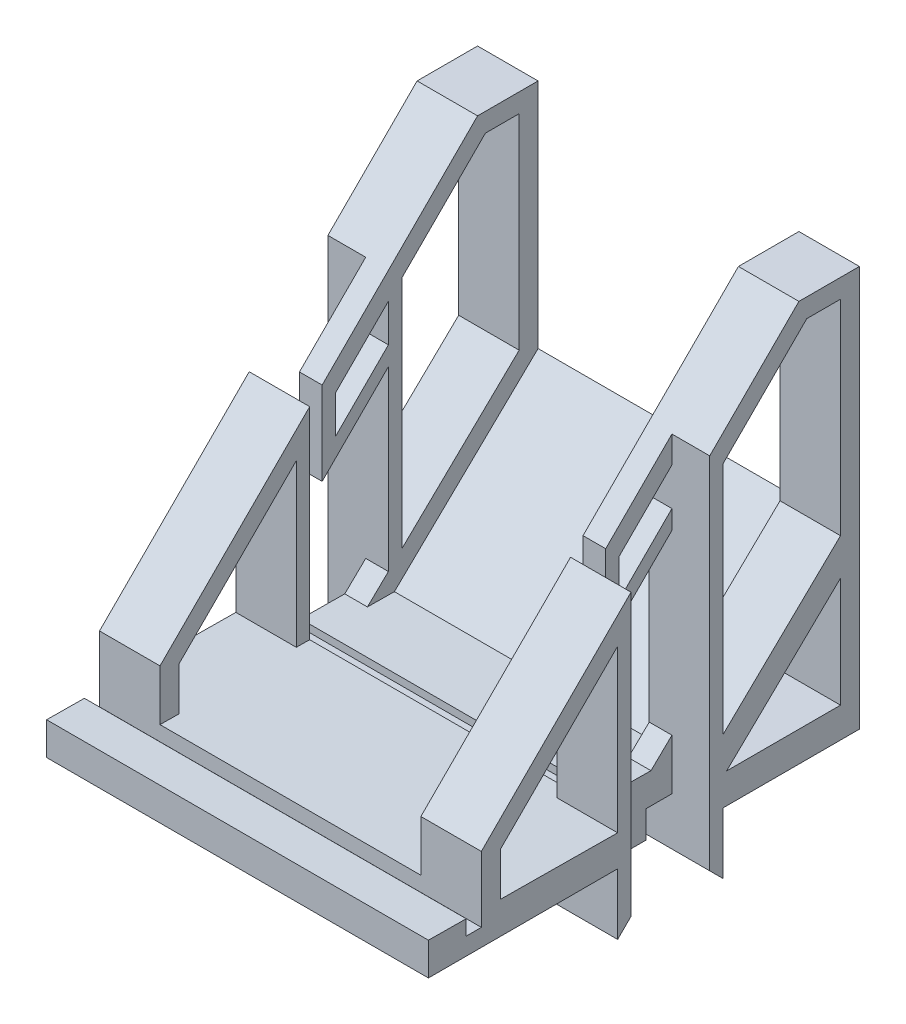
SolidWorks part; units mm, degrees
note: The reader was unsure of these and kept them because the rebuilt part matched: shared geometry of "Sketch1<3>", "Sketch9<3>".
ref_plane "Front Plane" through (0, 0, 0) normal (0, 0, 1) x (1, 0, 0)
ref_plane "Top Plane" through (0, 0, 0) normal (0, 1, 0) x (1, 0, 0)
ref_plane "Right Plane" through (0, 0, 0) normal (1, 0, 0) x (0, 0, -1)
sketch "Sketch1" plane through (0, 0, 0) normal (1, 0, 0) x (0, 0, -1)
  line L0 (0, 0) -> (5, 0)
  line L1 (5, 0) -> (5, -1.7)
  line L2 (5, -1.7) -> (7, -1.7)
  line L3 (7, -1.7) -> (7, 0)
  line L4 (7, 0) -> (38, 0)
  line L5 (38, 0) -> (57, 18.3481)
  line L6 (57, 18.3481) -> (57, -4)
  line L7 (57, -4) -> (33.8, -4)
  line L9 (33.8, -7.6) -> (30.2, -7.6)
  line L11 (30.2, -4) -> (0, -4)
  line L12 (0, -4) -> (0, 0)
  line L13 (30.2, -4) -> (33.8, -4) construction
  line L14 (54.5, 14.5437) -> (39.4396, 0)
  line L15 (39.4396, 0) -> (54.5, 0)
  line L16 (54.5, 0) -> (54.5, 14.5437)
  line L17 (26.795, -4) -> (26.795, -10.3322)
  line L18 (26.795, -10.3322) -> (25.0272, -12.1)
  line L19 (25.0272, -12.1) -> (25.0272, -4)
  line L20 (25.0272, -4) -> (26.795, -4)
  line L21 (37.205, -4) -> (37.205, -10.3322)
  line L22 (37.205, -10.3322) -> (38.9728, -12.1)
  line L23 (38.9728, -12.1) -> (38.9728, -4)
  line L24 (38.9728, -4) -> (37.205, -4)
  line L25 (26.795, -10.3322) -> (37.205, -10.3322) construction
  line L26 (33.8, -4) -> (33.8, -7.6)
  line L27 (30.2, -4) -> (30.2, -7.6)
  line L28 (38, 0) -> (7, 0.2705)
  line L29 (7, 0.2705) -> (7, 0)
  line L31 (38, 0) -> (7, 0)
  line L32 (5, 0) -> (5, 0.288)
  line L33 (5, 0.288) -> (0, 0.3316)
  line L34 (0, 0.3316) -> (0, 0)
  point P15 (32, -7.6)
  point P22 (32, -10.3322)
  point P30 (32, -4)
  dimension "D1" = 1.7
  dimension "D2" = 5
  dimension "D3" = 2
  dimension "D4" = 57
  dimension "D5" = 136
  dimension "D6" = 38
  dimension "D7" = 4
  dimension "D8" = 3.6
  dimension "D9" = 135
  dimension "D10" = 3.6
  dimension "D11" = 135
  dimension "D12" = 25
  dimension "D13" = 8.1
  dimension "D14" = 1
  dimension "D15" = 2.5
  dimension "D16" = 0.5
  dimension "D17" = 2.5
  dimension "D18" = 10.41
extrude "Boss-Extrude1" add sketch "Sketch1" along normal blind 17.25
sketch "Sketch3" plane through (17.25, 0, 0) normal (1, 0, 0) x (0, 0, -1)
  line L0 (57, -4) -> (57, 49)
  line L1 (57, 18.3481) -> (57, -4) construction
  line L2 (49, 49) -> (7, 7)
  line L3 (7, 7) -> (7, -1.7)
  line L5 (0, -4) -> (25.0272, -4)
  line L6 (38.9728, -4) -> (57, -4)
  line L8 (25.0272, -12.1) -> (25.0272, -4) construction
  line L9 (37.205, -10.3322) -> (38.9728, -12.1) construction
  line L10 (26.795, -10.3322) -> (25.0272, -12.1) construction
  line L11 (26.795, -4) -> (26.795, -10.3322) construction
  line L12 (30.2, -4) -> (26.795, -4) construction
  line L13 (33.8, -4) -> (33.8, -7.6)
  line L14 (33.8, -7.6) -> (30.2, -7.6) construction
  line L16 (37.205, -4) -> (33.8, -4) construction
  line L17 (38.9728, -12.1) -> (38.9728, -4) construction
  line L18 (37.205, -4) -> (37.205, -10.3322) construction
  line L19 (25.0272, -12.1) -> (25.0272, -4)
  line L20 (37.205, -10.3322) -> (38.9728, -12.1)
  line L21 (26.795, -10.3322) -> (25.0272, -12.1)
  line L22 (26.795, -4) -> (26.795, -10.3322)
  line L23 (30.2, -4) -> (26.795, -4)
  line L25 (33.8, -7.6) -> (30.2, -7.6)
  line L27 (37.205, -4) -> (33.8, -4)
  line L28 (38.9728, -12.1) -> (38.9728, -4)
  line L29 (37.205, -4) -> (37.205, -10.3322)
  line L30 (9.5, 5.9645) -> (9.5, 0)
  line L31 (7, 0) -> (38, 0) construction
  line L32 (9.5, 0) -> (34.4011, 0)
  line L33 (34.4011, 0) -> (54.5, 19.4093)
  line L34 (54.5, 19.4093) -> (54.5, 46.5)
  line L35 (50.0355, 46.5) -> (9.5, 5.9645)
  line L36 (0, -4) -> (0, 0) construction
  line L37 (38, 0) -> (57, 18.3481) construction
  line L38 (0, 0) -> (5, 0) construction
  line L39 (7, -1.7) -> (7, 0) construction
  line L40 (49, 49) -> (57, 49)
  line L41 (54.5, 46.5) -> (50.0355, 46.5)
  line L42 (5, 0) -> (5, -1.7) construction
  line L43 (5, -1.7) -> (7, -1.7) construction
  line L44 (0, -4) -> (0, 0)
  line L45 (0, 0) -> (5, 0)
  line L46 (5, 0) -> (5, -1.7)
  line L47 (5, -1.7) -> (7, -1.7)
  line L53 (30.2, -4) -> (30.2, -7.6)
  line L54 (39.4396, 0) -> (54.5, 0) construction
  line L55 (54.5, 0) -> (54.5, 14.5437) construction
  line L56 (54.5, 14.5437) -> (39.4396, 0) construction
  line L57 (39.4396, 0) -> (54.5, 0)
  line L58 (54.5, 0) -> (54.5, 14.5437)
  line L59 (54.5, 14.5437) -> (39.4396, 0)
  point P6 (53, 49)
  dimension "D1" = 45
  dimension "D7" = 8
  dimension "D2" = 11
  dimension "D3" = 2.5
  dimension "D4" = 2.5
  dimension "D5" = 2.5
  dimension "D6" = 2.5
  dimension "D8" = 2.5
extrude "Boss-Extrude2" add sketch "Sketch3" along normal blind 3
mirror "Mirror1" about plane through (0, 0, 0) normal (1, 0, 0) of "Boss-Extrude2", "Boss-Extrude1"
extrude "Boss-Extrude3" add sketch "Sketch1<3>" along normal up to surface and the other way up to surface contours L28 L29 L4 | L33 L34 L0 L32
sketch "Sketch1<3>" plane through (0, 0, 0) normal (1, 0, 0) x (0, 0, -1) same geometry as "Sketch1"
sketch "Sketch5" plane through (20.25, 0, 0) normal (1, 0, 0) x (0, 0, -1)
  line L0 (25.0272, -12.1) -> (26.795, -10.3322)
  line L1 (26.795, -10.3322) -> (26.795, 26.795)
  line L2 (49, 49) -> (7, 7) construction
  line L3 (26.795, 26.795) -> (25.0272, 25.0272)
  line L4 (25.0272, 25.0272) -> (25.0272, -12.1)
  line L5 (37.205, -10.3322) -> (38.9728, -12.1)
  line L6 (38.9728, -12.1) -> (38.9728, 38.9728)
  line L7 (38.9728, 38.9728) -> (37.205, 37.205)
  line L8 (37.205, 37.205) -> (37.205, -10.3322)
extrude "Boss-Extrude4" [suppressed] add sketch "Sketch5" along normal blind 5 and the other way up to surface contours L4 L0 L1 L3 | L6 L7 L8 L5
sketch "Sketch6" plane through (-20.25, 0, 0) normal (-1, 0, 0) x (0, 0, 1)
  line L0 (-37.205, 2.7077) -> (-37.205, 33.6695)
  line L1 (-37.205, 33.6695) -> (-38.9728, 35.4372)
  line L2 (-38.9728, 35.4372) -> (-38.9728, 4.4148)
  line L3 (-34.4333, 0.0311) -> (-54.5, 19.4093) construction
  line L4 (-38.9728, 35.4372) -> (-38.9728, 4.4148) construction
  line L5 (-38.9728, 4.4148) -> (-37.205, 2.7077)
  line L6 (-26.795, 0.0978) -> (-25.0272, 0.1132)
  line L7 (-25.0272, 0.1132) -> (-25.0272, 21.4917)
  line L8 (-25.0272, 21.4917) -> (-26.795, 23.2595)
  line L9 (-26.795, 23.2595) -> (-26.795, 0.0978)
  line L10 (-50.0355, 46.5) -> (-9.5, 5.9645) construction
  line L11 (-34.4333, 0.0311) -> (-9.5, 0.2487) construction
  dimension "D1" = 1.7678
  dimension "D2" = 1.7678
  dimension "D3" = 10.41
extrude "Boss-Extrude5" add sketch "Sketch6" against normal up to surface (3 mm away) contours L9 L6 L7 L8 | L2 L5 L0 L1 up to face at (-17.25, 20.1894, -35.6224)
sketch "Sketch7" plane through (0, 0, -38.9728) normal (0, 0, -1) x (-1, 0, 0)
  line L0 (-23.3701, 15.8617) -> (-23.3701, -0.8728) construction
  line L1 (-20.581, 15.8617) -> (-20.581, -0.8728)
  line L2 (-26.1592, 15.8617) -> (-26.1592, -0.8728)
  arc A0 (-20.581, 15.8617) -> (-26.1592, 15.8617) centre (-23.3701, 15.8617) ccw
  arc A1 (-26.1592, -0.8728) -> (-20.581, -0.8728) centre (-23.3701, -0.8728) ccw
  point P2 (-23.3701, 7.4945)
extrude "Cut-Extrude1" [suppressed] cut sketch "Sketch7" against normal up to surface (1.7678 mm away)
sketch "Sketch8" plane through (-20.25, 0, 0) normal (-1, 0, 0) x (0, 0, 1)
  line L0 (-25.0272, 21.4917) -> (-9.5, 5.9645) construction
  line L1 (-54.5, 46.5) -> (-50.0355, 46.5) construction
  line L2 (-50.0355, 46.5) -> (-38.9728, 35.4372) construction
  line L3 (-38.9728, 4.4148) -> (-54.5, 19.4093) construction
  line L4 (-54.5, 0) -> (-54.5, 14.5437) construction
  line L5 (-39.4396, 0) -> (-54.5, 0) construction
  line L6 (-54.5, 14.5437) -> (-39.4396, 0) construction
  line L7 (-25.0272, 0.1132) -> (-9.5, 0.2487) construction
  line L8 (-9.5, 5.9645) -> (-9.5, 0.2487) construction
  line L9 (-25.0272, 0.1132) -> (-25.0272, 21.4917) construction
  line L10 (-26.795, 23.2595) -> (-26.795, 0.0978) construction
  line L11 (-54.5, 19.4093) -> (-54.5, 46.5) construction
  line L12 (-38.9728, 35.4372) -> (-38.9728, 4.4148) construction
  line L13 (-37.205, 2.7077) -> (-37.205, 33.6695) construction
  line L14 (-25.0272, 21.4917) -> (-9.5, 5.9645)
  line L15 (-54.5, 46.5) -> (-50.0355, 46.5)
  line L16 (-50.0355, 46.5) -> (-38.9728, 35.4372)
  line L17 (-38.9728, 4.4148) -> (-54.5, 19.4093)
  line L18 (-54.5, 0) -> (-54.5, 14.5437)
  line L19 (-39.4396, 0) -> (-54.5, 0)
  line L20 (-54.5, 14.5437) -> (-39.4396, 0)
  line L21 (-5, -1.7) -> (-7, -1.7)
  line L22 (-7, -1.7) -> (-7, 7)
  line L23 (-7, 7) -> (-49, 49)
  line L24 (-49, 49) -> (-57, 49)
  line L25 (-57, 49) -> (-57, -4)
  line L26 (-57, -4) -> (-38.9728, -4)
  line L27 (-38.9728, -4) -> (-38.9728, -12.1)
  line L28 (-38.9728, -12.1) -> (-37.205, -10.3322)
  line L29 (-37.205, -10.3322) -> (-37.205, -4)
  line L30 (-37.205, -4) -> (-33.8, -4)
  line L31 (-33.8, -4) -> (-33.8, -7.6)
  line L32 (-33.8, -7.6) -> (-30.2, -7.6)
  line L33 (-30.2, -7.6) -> (-30.2, -4)
  line L34 (-30.2, -4) -> (-26.795, -4)
  line L35 (-26.795, -4) -> (-26.795, -10.3322)
  line L36 (-26.795, -10.3322) -> (-25.0272, -12.1)
  line L37 (-25.0272, -12.1) -> (-25.0272, -4)
  line L38 (-25.0272, -4) -> (0, -4)
  line L39 (0, -4) -> (0, 0.3316)
  line L40 (0, 0.3316) -> (-5, 0.288)
  line L41 (-5, 0.288) -> (-5, -1.7)
  line L42 (-5, -1.7) -> (-7, -1.7)
  line L43 (-7, -1.7) -> (-7, 7)
  line L44 (-7, 7) -> (-26.795, 26.795)
  line L45 (-49, 49) -> (-57, 49)
  line L46 (-57, 49) -> (-57, -4)
  line L47 (-57, -4) -> (-38.9728, -4)
  line L48 (-38.9728, -4) -> (-38.9728, -12.1)
  line L49 (-38.9728, -12.1) -> (-37.205, -10.3322)
  line L50 (-37.205, -10.3322) -> (-37.205, -4)
  line L56 (-26.795, -4) -> (-26.795, -10.3322)
  line L57 (-26.795, -10.3322) -> (-25.0272, -12.1)
  line L58 (-25.0272, -12.1) -> (-25.0272, -4)
  line L59 (-25.0272, -4) -> (0, -4)
  line L60 (0, -4) -> (0, 0.3316)
  line L61 (0, 0.3316) -> (-5, 0.288)
  line L62 (-5, 0.288) -> (-5, -1.7)
  line L63 (-25.0272, 0.1132) -> (-9.5, 0.2487)
  line L64 (-9.5, 5.9645) -> (-9.5, 0.2487)
  line L65 (-25.0272, 0.1132) -> (-25.0272, 21.4917)
  line L66 (-26.795, 23.2595) -> (-26.795, 0.0978)
  line L67 (-54.5, 19.4093) -> (-54.5, 46.5)
  line L68 (-38.9728, 35.4372) -> (-38.9728, 4.4148)
  line L69 (-37.205, 2.7077) -> (-37.205, 33.6695)
  line L70 (-37.205, 33.6695) -> (-37.205, 37.205)
  line L71 (-37.205, 2.7077) -> (-37.205, -4)
  line L72 (-26.795, 0.0978) -> (-26.795, -4)
  line L73 (-26.795, 23.2595) -> (-26.795, 26.795)
  line L74 (-37.205, 37.205) -> (-49, 49)
  line M39 (-37.205, 2.7077) -> (-37.205, 33.6695)
  line M41 (-26.795, 23.2595) -> (-26.795, 0.0978)
  line M43 (-50.0355, 46.5) -> (-38.9728, 35.4372)
  line M44 (-38.9728, 35.4372) -> (-38.9728, 4.4148)
  line M45 (-38.9728, 4.4148) -> (-54.5, 19.4093)
  line M46 (-54.5, 19.4093) -> (-54.5, 46.5)
  line M47 (-54.5, 46.5) -> (-50.0355, 46.5)
  line M48 (-25.0272, 0.1132) -> (-25.0272, 21.4917)
  line M49 (-25.0272, 21.4917) -> (-9.5, 5.9645)
  line M50 (-9.5, 5.9645) -> (-9.5, 0.2487)
  line M51 (-9.5, 0.2487) -> (-25.0272, 0.1132)
  line M52 (-5, -1.7) -> (-7, -1.7)
  line M53 (-7, -1.7) -> (-7, 7)
  line M54 (-7, 7) -> (-49, 49)
  line M55 (-49, 49) -> (-57, 49)
  line M56 (-57, 49) -> (-57, -4)
  line M57 (-57, -4) -> (-38.9728, -4)
  line M58 (-38.9728, -4) -> (-38.9728, -12.1)
  line M59 (-38.9728, -12.1) -> (-37.205, -10.3322)
  line M60 (-37.205, -10.3322) -> (-37.205, -4)
  line M66 (-26.795, -4) -> (-26.795, -10.3322)
  line M67 (-26.795, -10.3322) -> (-25.0272, -12.1)
  line M68 (-25.0272, -12.1) -> (-25.0272, -4)
  line M69 (-25.0272, -4) -> (0, -4)
  line M70 (0, -4) -> (0, 0.3316)
  line M71 (0, 0.3316) -> (-5, 0.288)
  line M72 (-5, 0.288) -> (-5, -1.7)
  line M73 (-54.5, 14.5437) -> (-39.4396, 0)
  line M74 (-39.4396, 0) -> (-54.5, 0)
  line M75 (-54.5, 0) -> (-54.5, 14.5437)
  dimension "D1" = 0
extrude "Boss-Extrude6" add sketch "Sketch8" along normal blind 5 contours L71 L70 M39 M54 M55 M56 M57 M58 M59 M60 M75 M73 M74 M47 M43 M44 M45 M46 | L73 L72 M41 M66 M67 M68 M69 M70 M71 M72 M52 M53 M54 M51 M48 M49 M50
sketch "Sketch9" plane through (-20.25, 0, 0) normal (-1, 0, 0) x (0, 0, 1)
  line L0 (-26.795, 26.795) -> (-26.795, 23.2595)
  line L1 (-26.795, 23.2595) -> (-28.445, 24.9095)
  line L2 (-37.205, 33.6695) -> (-26.795, 23.2595) construction
  line L3 (-28.445, 24.9095) -> (-28.445, 28.445)
  line L4 (-37.205, 37.205) -> (-26.795, 26.795) construction
  line L5 (-28.445, 28.445) -> (-26.795, 26.795)
  line L6 (-28.445, 24.9095) -> (-28.445, 17.4063)
  line L7 (-26.795, 0.0978) -> (-28.595, 0.0978)
  line L8 (-26.795, 0.0978) -> (-26.795, -0.9022)
  line L9 (-26.795, -0.9022) -> (-28.595, -0.9022)
  line L10 (-28.595, 0.0978) -> (-28.595, -0.9022)
  line L12 (-30.215, 21.6795) -> (-30.215, 26.6795)
  line L13 (-28.445, 24.9095) -> (-30.215, 26.6795)
  line L14 (-28.445, 17.4063) -> (-37.205, 26.1663)
  line L15 (-37.205, 37.205) -> (-37.205, -10.3322) construction
  line L16 (-30.215, 21.6795) -> (-37.205, 28.6695)
  line L17 (-37.205, 28.6695) -> (-37.205, 26.1663)
  line M3 (-26.795, 23.2595) -> (-26.795, 26.795)
  line M4 (-26.795, 26.795) -> (-37.205, 37.205)
  line M6 (-37.205, 33.6695) -> (-26.795, 23.2595)
  dimension "D1" = 1.65
  dimension "D2" = 1
  dimension "D3" = 5
  dimension "D4" = 1.77
  dimension "D5" = 1.8
  dimension "D6" = 1.77
extrude "Cut-Extrude2" cut sketch "Sketch9" against normal up to surface (20.25 mm away) contours L3 M6 M3 M4 | L7 L10 L9 L8
extrude "Boss-Extrude7" add sketch "Sketch9<3>" against normal blind 3
sketch "Sketch9<3>" plane through (-20.25, 0, 0) normal (-1, 0, 0) x (0, 0, 1) same geometry as "Sketch9"
mirror "Mirror2" about plane through (0, 0, 0) normal (1, 0, 0) of "Boss-Extrude7", "Boss-Extrude5", "Boss-Extrude6", "Cut-Extrude2"
equation "\"beam\"= 2.5mm"
equation "\"D3@Sketch3\"=\"beam\""
equation "\"D4@Sketch3\"=\"beam\""
equation "\"D5@Sketch3\"=\"beam\""
equation "\"D6@Sketch3\"=\"beam\""
equation "\"D8@Sketch3\"=\"beam\""
